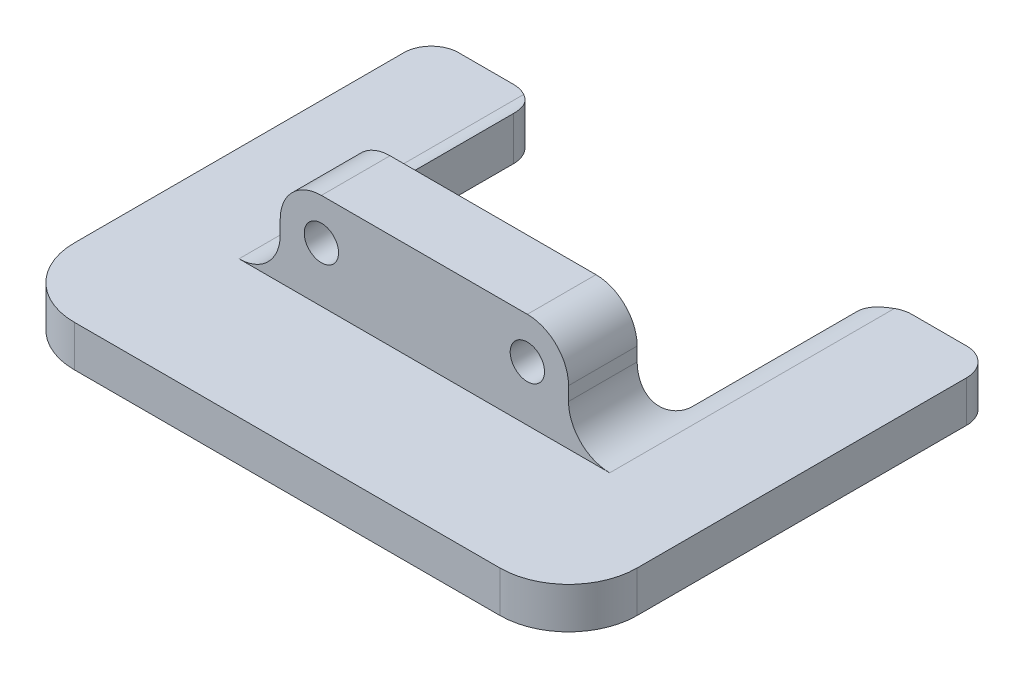
SolidWorks part; units mm, degrees
material "ABS"
ref_plane "正面" through (0, 0, 0) normal (0, 0, 1) x (1, 0, 0)
ref_plane "平面" through (0, 0, 0) normal (0, 1, 0) x (1, 0, 0)
ref_plane "右側面" through (0, 0, 0) normal (1, 0, 0) x (0, 0, -1)
sketch "ｽｹｯﾁ1" plane through (0, 0, 0) normal (0, 0, 1) x (1, 0, 0)
  line L1 (-3, -4) -> (18, -4)
  line L2 (-3, -4) -> (-3, 0)
  line L3 (0, 3) -> (15, 3)
  line L4 (18, -4) -> (18, 0)
  circle A0 centre (0, 0) radius 1.25
  circle A1 centre (15, 0) radius 1.25
  arc A2 (15, 3) -> (18, 0) centre (15, 0) cw
  arc A3 (-3, 0) -> (0, 3) centre (0, 0) cw
  dimension "D1" = 2.5
  dimension "D2" = 15
  dimension "D3" = 3
  dimension "D4" = 4
extrude "ﾎﾞｽ - 押し出し1" add sketch "ｽｹｯﾁ1" along normal blind 5
sketch "ｽｹｯﾁ2" plane through (0, -4, 0) normal (0, -1, 0) x (1, 0, 0)
  line L0 (-3, 5) -> (18, 5) construction
  line L1 (-13, 0) -> (28, 0)
  line L2 (-13, 0) -> (-13, 15)
  line L3 (-13, 15) -> (28, 15)
  line L4 (28, 0) -> (28, 15)
  line L5 (-3, 0) -> (18, 0) construction
  line L6 (-3, 5) -> (-3, 0) construction
  line L7 (18, 5) -> (18, 0) construction
  dimension "D1" = 0
  dimension "D2" = 10
  dimension "D3" = 10
  dimension "D4" = 10
extrude "ﾎﾞｽ - 押し出し2" add sketch "ｽｹｯﾁ2" along normal blind 3
sketch "ｽｹｯﾁ4" plane through (0, -4, 0) normal (0, 1, 0) x (1, 0, 0)
  line L0 (-13, 0) -> (-3, 0) construction
  line L1 (-13, 0) -> (-5, 0)
  line L2 (-13, 0) -> (-13, 16)
  line L3 (-13, 16) -> (-5, 16)
  line L4 (-5, 0) -> (-5, 16)
  line L5 (28, 0) -> (20, 0)
  line L6 (28, 0) -> (28, 16)
  line L7 (28, 16) -> (20, 16)
  line L8 (20, 0) -> (20, 16)
  line L9 (28, 0) -> (28, -15) construction
  dimension "D1" = 8
  dimension "D2" = 16
extrude "ﾎﾞｽ - 押し出し3" add sketch "ｽｹｯﾁ4" against normal up to surface (3 mm away) up to face at (7.5, -7, 7.5)
fillet "ﾌｨﾚｯﾄ1" radius 3 2 edges at (-3, -4, 2.5) (18, -4, 2.5)
fillet "ﾌｨﾚｯﾄ2" radius 5 2 edges at (-13, -5.5, 15) (28, -5.5, 15)
fillet "ﾌｨﾚｯﾄ3" radius 2 6 edges at (28, -5.5, -16) (20, -5.4142, -16) (20, -5.4142, 0) (-5, -5.4142, 0) (-5, -5.4142, -16) (-13, -5.5, -16)
